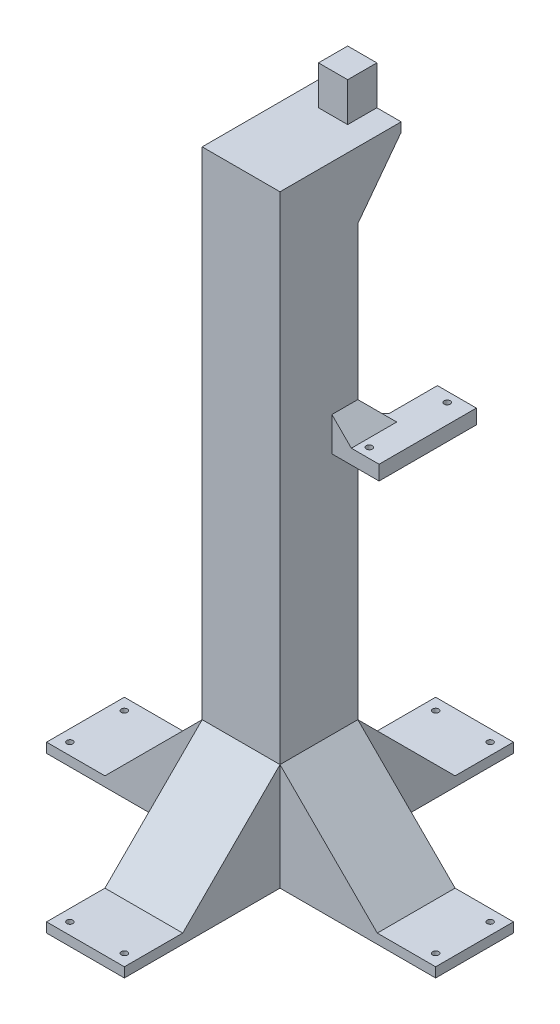
SolidWorks part; units mm, degrees
ref_plane "Front Plane" through (0, 0, 0) normal (0, 0, 1) x (1, 0, 0)
ref_plane "Top Plane" through (0, 0, 0) normal (0, 1, 0) x (1, 0, 0)
ref_plane "Right Plane" through (0, 0, 0) normal (1, 0, 0) x (0, 0, -1)
sketch "Sketch1" plane through (0, 0, 0) normal (0, 1, 0) x (1, 0, 0)
  line L0 (0, 0) -> (-40, 0) construction
  line L1 (0, 0) -> (80, 0)
  line L2 (0, 0) -> (0, 40)
  line L3 (0, 40) -> (80, 40)
  line L4 (80, 0) -> (80, 40)
  line L8 (-40, 40) -> (-40, 0)
  line L9 (-40, 40) -> (0, 0) construction
  line L10 (-40, 40) -> (0, 40)
  line L11 (-40, 40) -> (-40, 0)
  line L12 (-40, 0) -> (0, 0)
  line L13 (0, 40) -> (0, 0)
  line L14 (-40, 0) -> (0, 40) construction
  line L15 (-40, 0) -> (-40, -80)
  line L16 (0, 0) -> (0, -80)
  line L17 (-40, -80) -> (0, -80)
  line L18 (-40, 0) -> (0, 0)
  line L19 (-40, 40) -> (-120, 40)
  line L20 (-40, 0) -> (-120, 0)
  line L21 (-120, 40) -> (-120, 0)
  line L22 (-40, 40) -> (-40, 0)
  line L23 (0, 40) -> (0, 120)
  line L24 (-40, 40) -> (-40, 120)
  line L25 (0, 120) -> (-40, 120)
  line L26 (0, 40) -> (-40, 40)
  circle A5 centre (74, 34) radius 1.55
  circle A7 centre (74, 6) radius 1.55
  circle A9 centre (-6, -74) radius 1.55
  circle A11 centre (-34, -74) radius 1.55
  circle A13 centre (-114, 6) radius 1.55
  circle A15 centre (-114, 34) radius 1.55
  circle A17 centre (-34, 114) radius 1.55
  circle A19 centre (-6, 114) radius 1.55
  point P7 (0, 0)
  point P9 (0, 0)
  point P10 (0, 0)
  point P11 (-20, 20)
  point P17 (0, 0)
  point P56 (-20, 20)
  dimension "D4" = 4
  dimension "D11" = 3.1
  dimension "D13" = 3.1
  dimension "D3" = 40
  dimension "D5" = 80
  dimension "D24" = 6
  dimension "D25" = 6
  dimension "D26" = 6
  dimension "D27" = 6
extrude "Boss-Extrude1" add sketch "Sketch1" along normal blind 5 contours L1 L4 L3 L2 A7 A5 | L23 L25 L24 L10 A19 A17 | L19 L21 L20 L8 A15 A13 | L15 L17 L16 L12 A11 A9 region at (39.8389, 0, -20) region at (-20, 0, 39.8389) region at (-20, 0, -79.8389) region at (-79.8389, 0, -20)
extrude "Boss-Extrude2" add sketch "Sketch1<4>" along normal blind 310 contours L8 L12 L2 L10 region at (-20, 0, -20)
sketch "Sketch1<4>" plane through (0, 0, 0) normal (0, 1, 0) x (1, 0, 0) same geometry as "Sketch1"
chamfer "Chamfer1" distance 50 angle 45 2 edges at (-40, 5, -20) (0, 5, -20)
chamfer "Chamfer2" distance 50 angle 45 2 edges at (-20, 5, -40) (-20, 5, 0)
sketch "Sketch2" plane through (0, 0, 0) normal (0, 1, 0) x (1, 0, 0)
  line L1 (-64.25, 76.68) -> (-44.25, 76.68)
  line L2 (-64.25, 76.68) -> (-64.25, 26.68)
  line L3 (-64.25, 26.68) -> (-40, 26.68)
  line L9 (4.25, 76.68) -> (24.25, 76.68)
  line L12 (24.25, 76.68) -> (24.25, 26.68)
  line L17 (-40, 26.68) -> (24.25, 26.68)
  line L18 (-54.25, 71.68) -> (14.25, 71.68) construction
  line L19 (14.25, 71.68) -> (14.25, 31.68) construction
  line L20 (-20, 71.68) -> (-20, 40) construction
  line L21 (0, 40) -> (-40, 40) construction
  line L22 (-40, 40) -> (-40, 0) construction
  line L23 (-64.25, 71.68) -> (-44.25, 71.68) construction
  line L25 (4.25, 71.68) -> (24.25, 71.68) construction
  line L26 (-44.25, 51.75) -> (-32.5, 40)
  line L27 (4.25, 51.75) -> (-7.5, 40)
  line L28 (4.25, 76.68) -> (4.25, 51.75)
  line L29 (-44.25, 76.68) -> (-44.25, 51.75)
  line L30 (-32.5, 40) -> (-7.5, 40)
  line L31 (-40, 40) -> (0, 40) construction
  circle A0 centre (-54.25, 71.68) radius 1.55
  circle A1 centre (14.25, 71.68) radius 1.55
  circle A2 centre (-54.25, 31.68) radius 1.55
  circle A3 centre (14.25, 31.68) radius 1.55
  point P4 (-20, 40)
  point P14 (0, 0)
  point P16 (14.25, 71.68)
  point P24 (-54.25, 71.68)
  point P29 (-20, 40)
  point P36 (0, 0)
  dimension "D4" = 3.1
  dimension "D5" = 3.1
  dimension "D9" = 3.1
  dimension "D13" = 3.1
  dimension "D1" = 68.5
  dimension "D2" = 20
  dimension "D3" = 5
  dimension "D6" = 31.68
  dimension "D7" = 20
  dimension "D8" = 40
  dimension "D10" = 5
  dimension "D11" = 5
  dimension "D12" = 10
  dimension "D14" = 5
  dimension "D15" = 45
  dimension "D16" = 45
  dimension "D17" = 25
extrude "Boss-Extrude3" add sketch "Sketch2" along normal blind 7.5 from offset 180
chamfer "Chamfer7" distance 10 angle 45 4 edges at (-40, 187.5, -33.34) (0, 187.5, -33.34) (-36.25, 187.5, -40) (-3.75, 187.5, -40)
sketch "Sketch3" plane through (0, 310, 0) normal (0, 1, 0) x (1, 0, 0)
  line L1 (-27.5, 62.28) -> (-12.5, 62.28)
  line L2 (-27.5, 62.28) -> (-27.5, 47.28)
  line L3 (-27.5, 47.28) -> (-12.5, 47.28)
  line L4 (-12.5, 62.28) -> (-12.5, 47.28)
  line L5 (-20, 40) -> (-20, 47.28) construction
  line L6 (0, 40) -> (-40, 40) construction
  point P5 (-20, 47.28)
  point P6 (-54.25, 71.68)
  point P14 (-27.5, 54.78)
  dimension "D1" = 16.9
  dimension "D2" = 15
  dimension "D3" = 15
extrude "Boss-Extrude4" add sketch "Sketch3" along normal blind 20 separate body
sketch "Sketch4" plane through (0, 310, 0) normal (0, 1, 0) x (1, 0, 0)
  line L0 (-40, 40) -> (-40, 62.28)
  line L1 (-40, 40) -> (-40, 90) construction
  line L2 (-40, 62.28) -> (0, 62.28)
  line L3 (0, 62.28) -> (0, 40)
  line L4 (0, 40) -> (-40, 40)
  line L5 (-12.5, 62.28) -> (-27.5, 62.28) construction
extrude "Boss-Extrude5" add sketch "Sketch4" against normal blind 5
chamfer "Chamfer8" distance 22 angle 53 1 edges at (-20, 305, -40) first distance on face at (-20, 305, -51.14)
